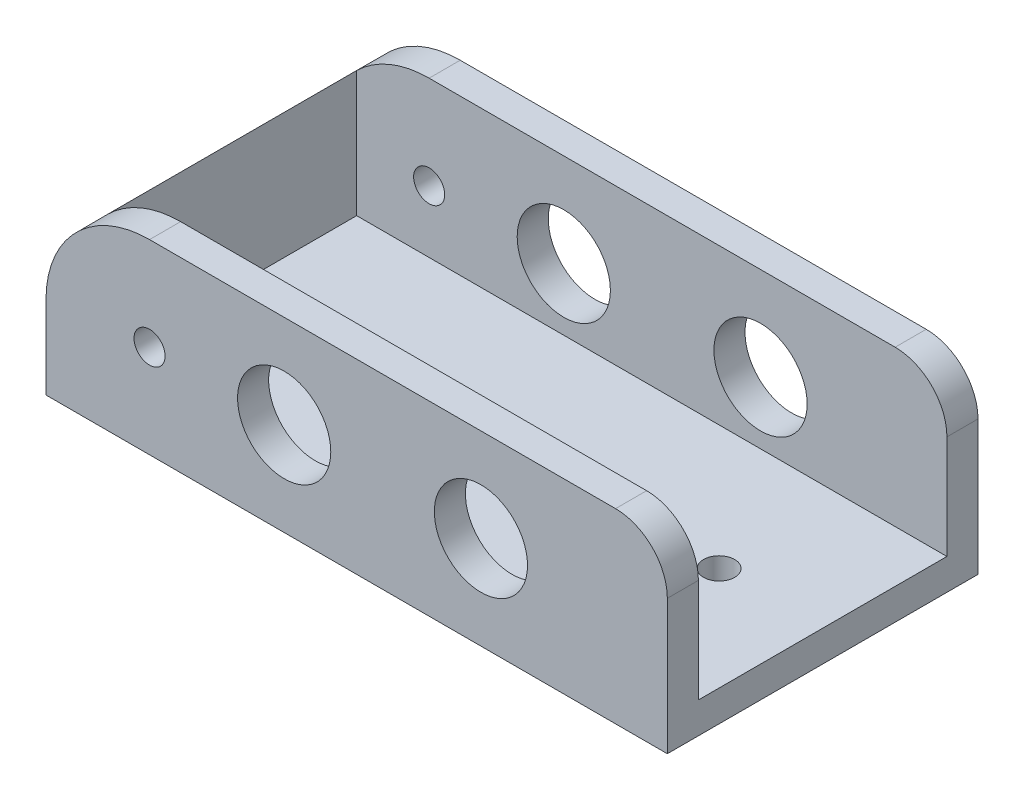
SolidWorks part; units mm, degrees
ref_plane "Alzado" through (0, 0, 0) normal (0, 0, 1) x (1, 0, 0)
ref_plane "Planta" through (0, 0, 0) normal (0, 1, 0) x (1, 0, 0)
ref_plane "Vista lateral" through (0, 0, 0) normal (1, 0, 0) x (0, 0, -1)
sketch "Croquis1" plane through (0, 0, 0) normal (0, 1, 0) x (1, 0, 0)
  line L0 (0, 15) -> (60, 15) construction
  line L1 (0, 0) -> (60, 0)
  line L2 (0, 0) -> (0, 30)
  line L3 (0, 30) -> (60, 30)
  line L4 (60, 0) -> (60, 30)
  circle A0 centre (10, 15) radius 1.5
  circle A1 centre (50, 15) radius 1.5
  dimension "D3" = 3
  dimension "D4" = 3
  dimension "D1" = 30
  dimension "D2" = 60
  dimension "D5" = 10
  dimension "D6" = 10
extrude "Saliente-Extruir1" add sketch "Croquis1" along normal blind 3
sketch "Croquis2" plane through (0, 3, 0) normal (0, 1, 0) x (1, 0, 0)
  line L0 (60, 0) -> (60, 30) construction
  line L1 (0, 30) -> (60, 30)
  line L3 (3, 27) -> (60, 27)
  line L4 (60, 30) -> (60, 27)
  line L5 (3, 27) -> (3, 3)
  line L6 (0, 0) -> (60, 0)
  line L8 (3, 3) -> (60, 3)
  line L9 (60, 0) -> (60, 3)
  line L10 (0, 30) -> (0, 0) construction
  line L11 (0, 30) -> (0, 0)
  dimension "D1" = 3
  dimension "D2" = 3
  dimension "D3" = 3
extrude "Saliente-Extruir2" add sketch "Croquis2" along normal blind 15
fillet "Redondeo1" radius 10 1 edges at (0, 18, -15)
fillet "Redondeo2" radius 5 2 edges at (60, 18, -28.5) (60, 18, -1.5)
sketch "Croquis3" plane through (0, 0, 0) normal (0, 0, 1) x (1, 0, 0)
  line L0 (60, 9) -> (0.0501, 9) construction
  line L1 (60, 13) -> (60, 0) construction
  line L2 (0, 0) -> (60, 0) construction
  line L3 (0, 8) -> (0, 0) construction
  line L4 (10, 18) -> (10, 0) construction
  arc A0 (10, 18) -> (0, 8) centre (10, 8) ccw construction
  circle A1 centre (42, 9) radius 4.5
  circle A2 centre (23, 9) radius 4.5
  circle A3 centre (10, 9) radius 1.5
  dimension "D2" = 9
  dimension "D3" = 9
  dimension "D6" = 3
  dimension "D1" = 9
  dimension "D4" = 23
  dimension "D5" = 18
extrude "Cortar-Extruir1" cut sketch "Croquis3" against normal blind 36
